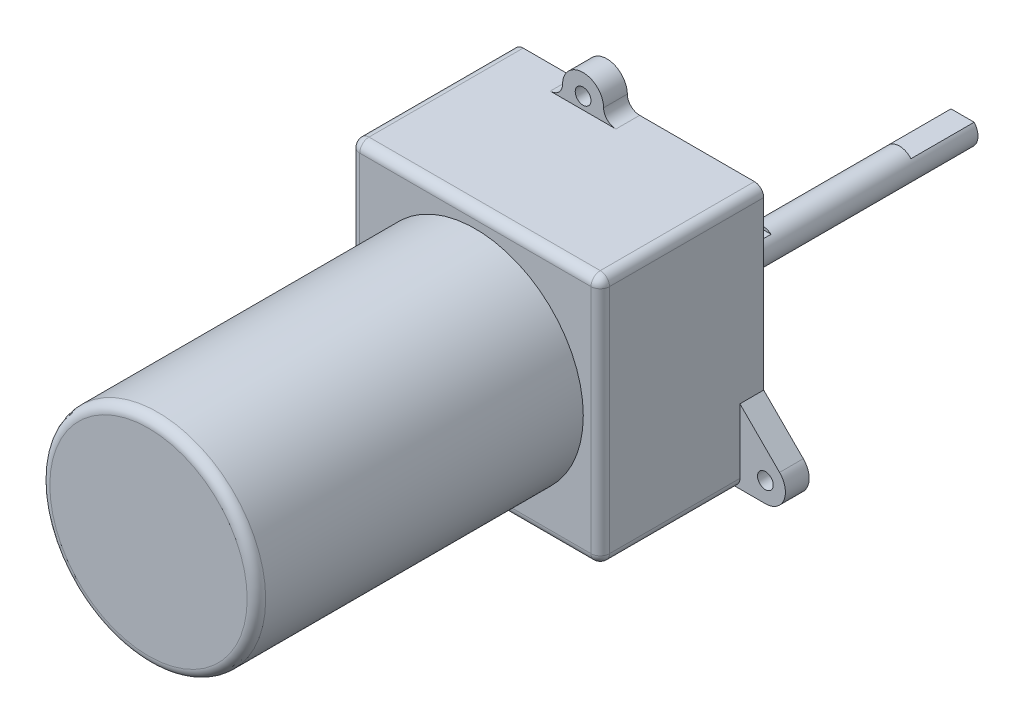
SolidWorks part; units mm, degrees
material "Alloy Steel"
ref_plane "Front Plane" through (0, 0, 0) normal (0, 0, 1) x (1, 0, 0)
ref_plane "Top Plane" through (0, 0, 0) normal (0, 1, 0) x (1, 0, 0)
ref_plane "Right Plane" through (0, 0, 0) normal (1, 0, 0) x (0, 0, -1)
sketch "Sketch1" plane through (0, 0, 0) normal (0, 0, 1) x (1, 0, 0)
  line L0 (40.5, 0) -> (-40.5, 0) construction
  line L1 (-40.5, 56) -> (40.5, 56)
  line L2 (-40.5, 56) -> (-40.5, -25)
  line L3 (-40.5, -25) -> (40.5, -25)
  line L4 (40.5, 56) -> (40.5, -25)
  point P4 (0, 0)
  point P8 (0, 0)
  dimension "D1" = 81
  dimension "D2" = 25
extrude "Boss-Extrude1" add sketch "Sketch1" along normal blind 53
sketch "Sketch2" plane through (0, 0, 53) normal (0, 0, 1) x (1, 0, 0)
  line L0 (0, 56) -> (0, -25) construction
  line L1 (40.5, 56) -> (-40.5, 56) construction
  line L2 (-40.5, -25) -> (40.5, -25) construction
  circle A0 centre (0, 15.5) radius 35
  dimension "D1" = 70
extrude "Boss-Extrude2" add sketch "Sketch2" along normal blind 106
sketch "Sketch3" plane through (0, 0, 0) normal (0, 0, 1) x (1, 0, 0)
  circle A0 centre (0, 0) radius 5
extrude "Boss-Extrude3" add sketch "Sketch3" against normal blind 105
sketch "Sketch4" plane through (0, 0, 0) normal (0, 0, 1) x (1, 0, 0)
  line L0 (48.75, -18.5) -> (-48.75, -18.5) construction
  line L1 (-48.75, -18.5) -> (-10.369, 59.9104) construction
  line L2 (-10.369, 59.9104) -> (48.75, -18.5) construction
  line L3 (0, -50.3582) -> (0, 50.3582) construction
  line L5 (-40.5, -25) -> (40.5, -25) construction
  line L6 (-48.75, -25) -> (48.75, -25)
  line L7 (-53.3462, -13.9038) -> (-40.5, -1.0576)
  line L8 (-40.5, 56) -> (-40.5, -25) construction
  line L9 (-40.5, -1.0576) -> (-40.5, 56)
  line L10 (-40.5, 56) -> (-17.019, 56)
  line L11 (40.5, 56) -> (-40.5, 56) construction
  line L12 (-3.719, 59.9104) -> (-17.019, 59.9104) construction
  line L13 (-17.019, 56) -> (-17.019, 59.9104)
  line L14 (-3.719, 59.9104) -> (-3.719, 56)
  line L15 (-3.719, 56) -> (40.5, 56)
  line L16 (40.5, 56) -> (40.5, -1.0576)
  line L17 (40.5, -25) -> (40.5, 56) construction
  line L18 (40.5, -1.0576) -> (53.3462, -13.9038)
  circle A0 centre (-48.75, -18.5) radius 2.55
  circle A1 centre (48.75, -18.5) radius 2.55
  circle A2 centre (-10.369, 59.9104) radius 2.55
  arc A3 (-48.75, -25) -> (-53.3462, -13.9038) centre (-48.75, -18.5) cw
  arc A4 (48.75, -25) -> (53.3462, -13.9038) centre (48.75, -18.5) ccw
  arc A5 (-3.719, 59.9104) -> (-17.019, 59.9104) centre (-10.369, 59.9104) ccw
  point P0 (-10.369, 59.9104)
  point P1 (-48.75, -18.5)
  point P2 (48.75, -18.5)
  point P5 (0, -18.5)
  dimension "D5" = 5.1
  dimension "D1" = 97.5
  dimension "D2" = 87.3
  dimension "D3" = 98.2
  dimension "D4" = 6.5
  dimension "D6" = 13.3
  dimension "D7" = 45
  dimension "D8" = 45
extrude "Boss-Extrude4" add sketch "Sketch4" along normal blind 7.7
fillet "Fillet1" radius 4 2 edges at (-17.019, 56, 3.85) (-3.719, 56, 3.85)
fillet "Fillet2" radius 3 9 edges at (0, 56, 53) (40.5, 15.5, 53) (0, -25, 53) (-40.5, 15.5, 53) (35, 15.5, 159) (40.5, -25, 30.35) (-40.5, -25, 30.35) (-40.5, 56, 26.5) (40.5, 56, 26.5)
sketch "Sketch5" plane through (0, 0, 0) normal (0, 0, 1) x (1, 0, 0)
  line L1 (9.6488, 11.3311) -> (-9.0418, 11.3311)
  line L2 (9.6488, 11.3311) -> (9.6488, 3.3)
  line L3 (9.6488, 3.3) -> (-9.0418, 3.3)
  line L4 (-9.0418, 11.3311) -> (-9.0418, 3.3)
  circle A0 centre (0, 0) radius 5 construction
  dimension "D1" = 3.3
extrude "Cut-Extrude1" cut sketch "Sketch5" against normal blind 30 from offset 84.5 offset against normal yes
sketch "Sketch6" plane through (0, 0, 0) normal (0, 0, 1) x (1, 0, 0)
  line L0 (8.2408, 7.651) -> (8.2408, 4)
  line L1 (8.2408, 4) -> (-4, 4)
  line L2 (-4, 4) -> (-4, -6.0442)
  line L3 (-4, -6.0442) -> (-7.3935, -6.0442)
  line L4 (-7.3935, -6.0442) -> (-7.3935, 7.651)
  line L5 (-7.3935, 7.651) -> (8.2408, 7.651)
  dimension "D1" = 4
  dimension "D2" = 4
extrude "Cut-Extrude2" cut sketch "Sketch6" against normal blind 7.2 from offset 32.7 offset against normal yes
